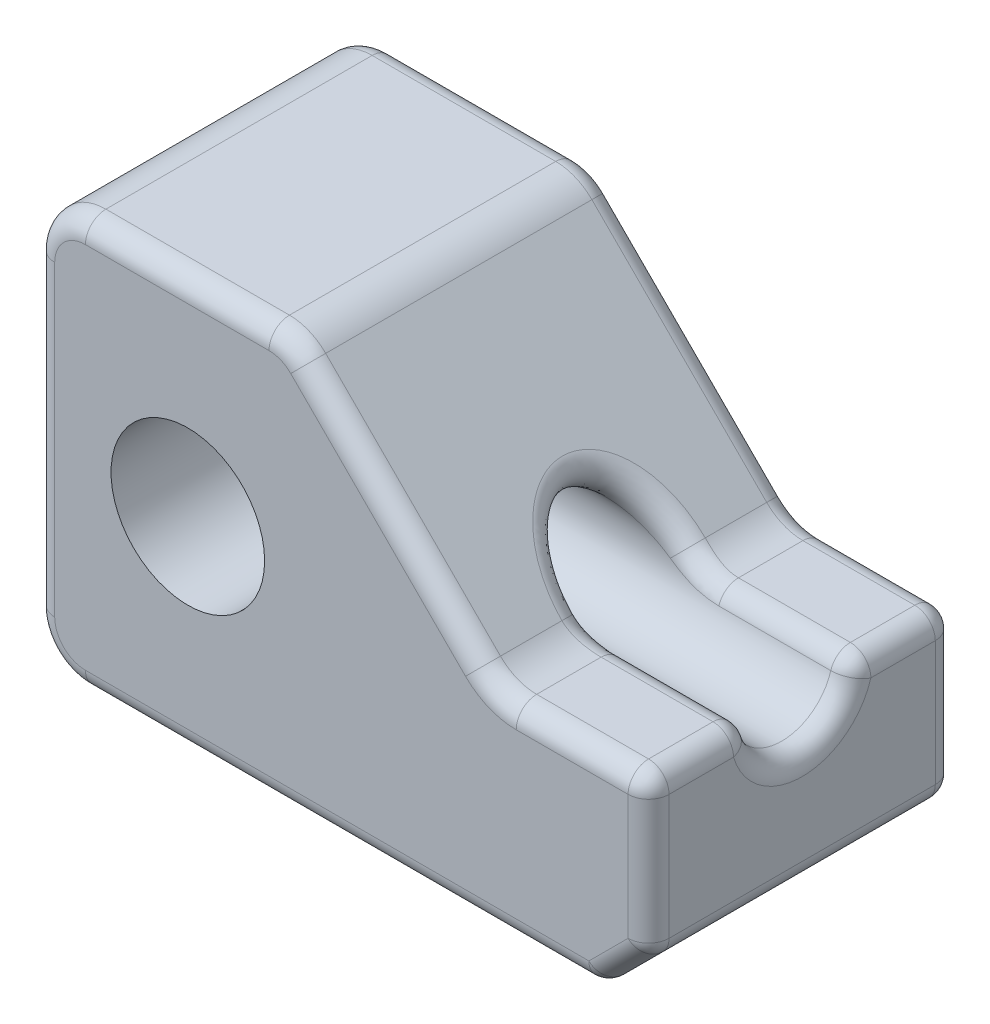
SolidWorks part; units mm, degrees
ref_plane "Front Plane" through (0, 0, 0) normal (0, 0, 1) x (1, 0, 0)
ref_plane "Top Plane" through (0, 0, 0) normal (0, 1, 0) x (1, 0, 0)
ref_plane "Right Plane" through (0, 0, 0) normal (1, 0, 0) x (0, 0, -1)
sketch "Sketch1" plane through (0, 0, 0) normal (0, 0, 1) x (1, 0, 0)
  line L0 (0, 0) -> (55, 0)
  line L1 (60, 5) -> (60, 20)
  line L2 (60, 20) -> (45, 20)
  line L3 (45, 20) -> (25, 40)
  line L4 (25, 40) -> (5, 40)
  line L5 (0, 35) -> (0, 0)
  line L6 (55, 0) -> (60, 5)
  circle A0 centre (15, 20) radius 7.5
  arc A1 (0, 35) -> (5, 40) centre (5, 35) cw
  point P1 (60, 0)
  point P11 (0, 40)
  dimension "D7" = 15
  dimension "D10" = 5
  dimension "D1" = 60
  dimension "D2" = 270
  dimension "D3" = 20
  dimension "D4" = 45
  dimension "D5" = 40
  dimension "D6" = 25
  dimension "D8" = 15
  dimension "D9" = 20
extrude "Boss-Extrude1" add sketch "Sketch1" along normal blind 15 and the other way blind 15
sketch "Sketch2" plane through (0, 0, 0) normal (-1, 0, 0) x (0, 0, 1)
  line L0 (-15, 0) -> (15, 0) construction
  circle A0 centre (0, 20) radius 5
  point P6 (-30.4016, 42.0063)
  dimension "D1" = 10
  dimension "D2" = 20
extrude "Cut-Extrude1" cut sketch "Sketch2" against normal up to surface (60 mm away) contours A0 up to face at (60, 12.5, 0)
fillet "Fillet1" radius 5 4 edges at (0, 0, 0) (45, 20, -10) (45, 20, 10) (25, 40, 0)
fillet "Fillet2" radius 2 32 edges at (24.8423, 39.6194, 15) (13.9645, 40, 15) (35, 30, 15) (1.4645, 38.5355, 15) (45.1577, 20.3806, 15) (0, 20, 15) (40, 25, 0) (53.5355, 20, 15) (44.7993, 20.5459, 4.9701) (1.4645, 1.4645, 15) (60, 12.5, 15) (45.4304, 20.2769, -4.9923) (60, 20, 10) (53.5355, 20, 5) (57.5, 2.5, 15) (30, 0, 15) (60, 5, 0) (53.5355, 20, -5) (60, 15, 0) (57.5, 2.5, -15) (55, 0, 0) (60, 12.5, -15) (60, 20, -10) (30, 0, -15) (53.5355, 20, -15) (1.4645, 1.4645, -15) (45.1577, 20.3806, -15) (0, 20, -15) (35, 30, -15) (1.4645, 38.5355, -15) (24.8423, 39.6194, -15) (13.9645, 40, -15)
